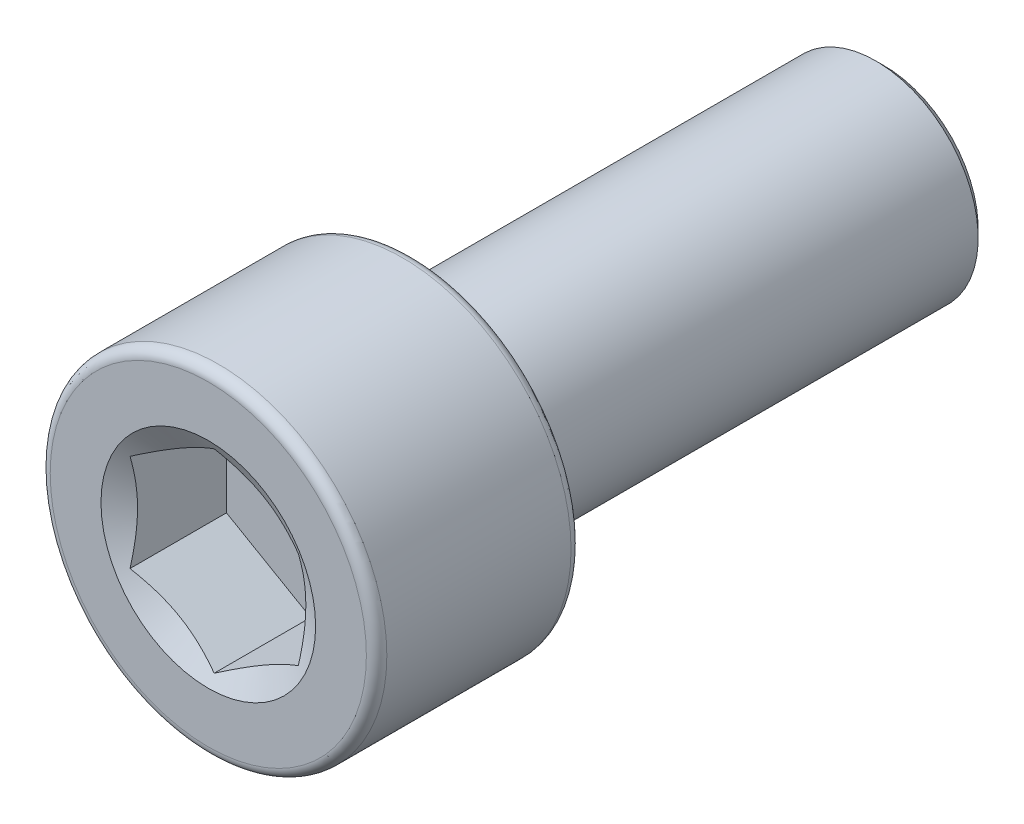
SolidWorks part; units mm, degrees
ref_plane "Front Plane" through (0, 0, 0) normal (0, 0, 1) x (1, 0, 0)
ref_plane "Top Plane" through (0, 0, 0) normal (0, 1, 0) x (1, 0, 0)
ref_plane "Right Plane" through (0, 0, 0) normal (1, 0, 0) x (0, 0, -1)
sketch "Sketch1" plane through (0, 0, 0) normal (1, 0, 0) x (0, 0, -1)
  line L0 (7.9693, 0) -> (-7.9693, 0) construction
  line L1 (-3.1433, 3.9687) -> (-3.1433, -3.9688) construction
  line L2 (7.9693, 2.413) -> (7.9693, -2.413) construction
  line L3 (7.9196, 2.4989) -> (8.3165, 1.8115) construction
  line L4 (8.2669, 1.8974) -> (8.3661, 1.8974) construction
  line L5 (8.3165, 1.8115) -> (8.7134, 2.4989) construction
  line L6 (8.7134, 2.4989) -> (7.9196, 2.4989) construction
  line L7 (8.3165, 1.8974) -> (8.3165, 1.8115) construction
  line L8 (8.3165, 2.4989) -> (8.3165, 2.413) construction
  line L9 (8.6638, 2.413) -> (7.9693, 2.413) construction
  point P4 (-3.1433, 0)
  point P6 (-3.1433, 1.9844)
  point P7 (5.1911, -2.413)
  point P20 (8.3165, 2.456)
  dimension "Head Height" = 4.826
  dimension "Head Diameter" = 7.9375
  dimension "Drive Size" = 3.9688
  dimension "Length" = 11.1125
  dimension "Screw Size Decimal Equivalent" = 4.826
  dimension "Pitch" = 0.7937
  dimension "Pitch/8" = 0.0992
  dimension "Thread Note" = 2.7781
sketch "Sketch2" plane through (0, 0, 0) normal (1, 0, 0) x (0, 0, -1)
  line L0 (7.9693, 0) -> (7.9693, 2.2146)
  line L1 (7.9693, 2.413) -> (7.9693, -2.413) construction
  line L2 (7.9693, 2.2146) -> (7.7708, 2.413)
  line L3 (7.7708, 2.413) -> (-3.1433, 2.413)
  line L4 (-3.1433, 2.413) -> (-3.1433, 3.7274)
  line L5 (-3.3846, 3.9687) -> (-7.728, 3.9687)
  line L6 (-7.9693, 3.7274) -> (-7.9693, 0)
  line L7 (7.9693, 0) -> (-7.9693, 0) construction
  line L8 (-7.9693, 0) -> (7.9693, 0)
  arc A0 (-3.1433, 3.7274) -> (-3.3846, 3.9687) centre (-3.3846, 3.7274) ccw
  arc A1 (-7.728, 3.9687) -> (-7.9693, 3.7274) centre (-7.728, 3.7274) ccw
  point P19 (-3.1433, 3.9687)
  dimension "D3" = 0.2413
  dimension "D1" = 0.1984
  dimension "D2" = 45
revolve "Revolve1" add sketch "Sketch2" angle 360 about L0
sketch "Sketch3" plane through (0, 0, 0) normal (0, 0, 1) x (1, 0, 0)
  line L1 (-1.9844, 1.1457) -> (-1.9844, -1.1457)
  line L2 (-1.9844, -1.1457) -> (0, -2.2914)
  line L3 (0, -2.2914) -> (1.9844, -1.1457)
  line L4 (1.9844, -1.1457) -> (1.9844, 1.1457)
  line L5 (1.9844, 1.1457) -> (0, 2.2914)
  line L6 (0, 2.2914) -> (-1.9844, 1.1457)
  circle A0 centre (0, 0) radius 1.9844 construction
  circle A1 centre (0, 0) radius 3.9687 construction
extrude "Cut-Extrude1" cut sketch "Sketch3" against normal blind 2.413 from vertex starting at point (0, 0, 7.9693)
sketch "Sketch4" plane through (0, 0, 7.9693) normal (0, 0, 1) x (1, 0, 0)
  line L0 (0, 2.2914) -> (0, 2.7701) construction
  line L1 (0, 2.7701) -> (0, 3.2488) construction
  line L2 (0, 3.2488) -> (0, 3.7274) construction
  circle A0 centre (0, 0) radius 2.5307
  point P12 (0, 2.5307)
extrude "Cut-Extrude2" cut sketch "Sketch4" against normal through all draft 60
split "Split1" [suppressed] bodies to split 106 112
sketch "Sketch5" [suppressed] plane through (0, 0, 0) normal (1, 0, 0) x (0, 0, -1)
  line L0 (8.2669, 1.8974) -> (8.3661, 1.8974)
  line L1 (8.3661, 1.8974) -> (8.6886, 2.456)
  line L2 (8.6886, 2.456) -> (7.9444, 2.456)
  line L3 (7.9444, 2.456) -> (8.2669, 1.8974)
  line L4 (7.9196, 2.4989) -> (8.3165, 1.8115) construction
sketch "Sketch6" [suppressed] plane through (0, 0, -7.9693) normal (0, 0, -1) x (-1, 0, 0)
  circle A0 centre (0, 0) radius 2.413
curve "Helix/Spiral1" [suppressed] pitch 0.7937 height 11.9062 turns 15
sweep "Cut-Sweep1" [suppressed] cut profiles "Sketch5" path "Helix/Spiral1"
sketch "Sketch7" [suppressed] plane through (0, 0, 3.1433) normal (0, 0, -1) x (-1, 0, 0)
  circle A0 centre (0, 0) radius 2.4638
  circle A1 centre (0, 0) radius 2.413 construction
  dimension "D1" = 0.0508
extrude "Boss-Extrude1" [suppressed] add sketch "Sketch7" along normal through all draft 20 and the other way blind 0.4826
ref_plane "Plane1" [suppressed] through (0, 0, 4.7358) normal (0, 0, -1) x (-1, 0, 0)
sketch "Sketch13" [suppressed] plane through (0, 0, 4.7358) normal (0, 0, -1) x (-1, 0, 0)
  line L0 (0.0992, 3.9675) -> (0, 0) construction
  line L1 (0, 0) -> (-0.0992, 3.9675) construction
  line L3 (0.0976, 3.902) -> (0.0992, 3.9675)
  line L6 (-0.0976, 3.902) -> (-0.0992, 3.9675)
  arc A1 (0.0992, 3.9675) -> (-0.0992, 3.9675) centre (0, 0) ccw
  circle A2 centre (0, 0) radius 3.9687 construction
  arc A3 (0.0976, 3.902) -> (-0.0976, 3.902) centre (0, 0) ccw
  point P2 (0, 3.9687)
  dimension "D1" = 0.1984
  dimension "D3" = 0.0655
extrude "Cut-Extrude3" [suppressed] cut sketch "Sketch13" against normal blind 2.6929
chamfer "Chamfer3" [suppressed] distance 0.0655 angle 60
chamfer "Chamfer4" [suppressed] distance 0.0655 angle 85
pattern_circular "CirPattern2" [suppressed] count 50 over 360 about axis through (0, 0, -7.9693) along (0, 0, 1) of bodies 134
equation "\"Pitch/8@Sketch1\" = \"Pitch@Sketch1\" / 8"
equation "\"Thread Note@Sketch1\" = \"Pitch@Sketch1\" * 3.5"
equation "\"D1@Sketch2\"=\"Pitch@Sketch1\"*.25"
equation "\"D3@Sketch2\"=\"Head Height@Sketch1\"*.05"
equation "\"D1@Cut-Extrude1\" = \"Head Height@Sketch1\" * .5"
equation "\"D3@Helix/Spiral1\" = \"Length@Sketch1\" + \"Pitch@Sketch1\""
equation "\"D4@Helix/Spiral1\" = \"Pitch@Sketch1\""
equation "\"D2@Boss-Extrude1\" = \"Head Height@Sketch1\" * .1"
equation "\"D1\"= \"Screw Size Decimal Equivalent@Sketch1\" * .4"
equation "\"D1@Plane1\"=\"Head Height@Sketch1\" * .33"
equation "\"D1@Cut-Extrude3\"=( \"Head Height@Sketch1\" - \"D1@Plane1\" - \"D3@Sketch2\" )  * .9"
equation "\"D1@Chamfer3\"=\"D3@Sketch13\""
equation "\"D1@Chamfer4\"=\"D3@Sketch13\""
equation "\"D1@CirPattern2\"=( \"Head Diameter@Sketch1\" * pi )  /  ( 2.5*\"D1@Sketch13\" )"
equation "\"D1@Sketch13\"=\"Head Diameter@Sketch1\" * .025"
equation "\"D3@Sketch13\"=\"D1@Sketch13\"*.33"
